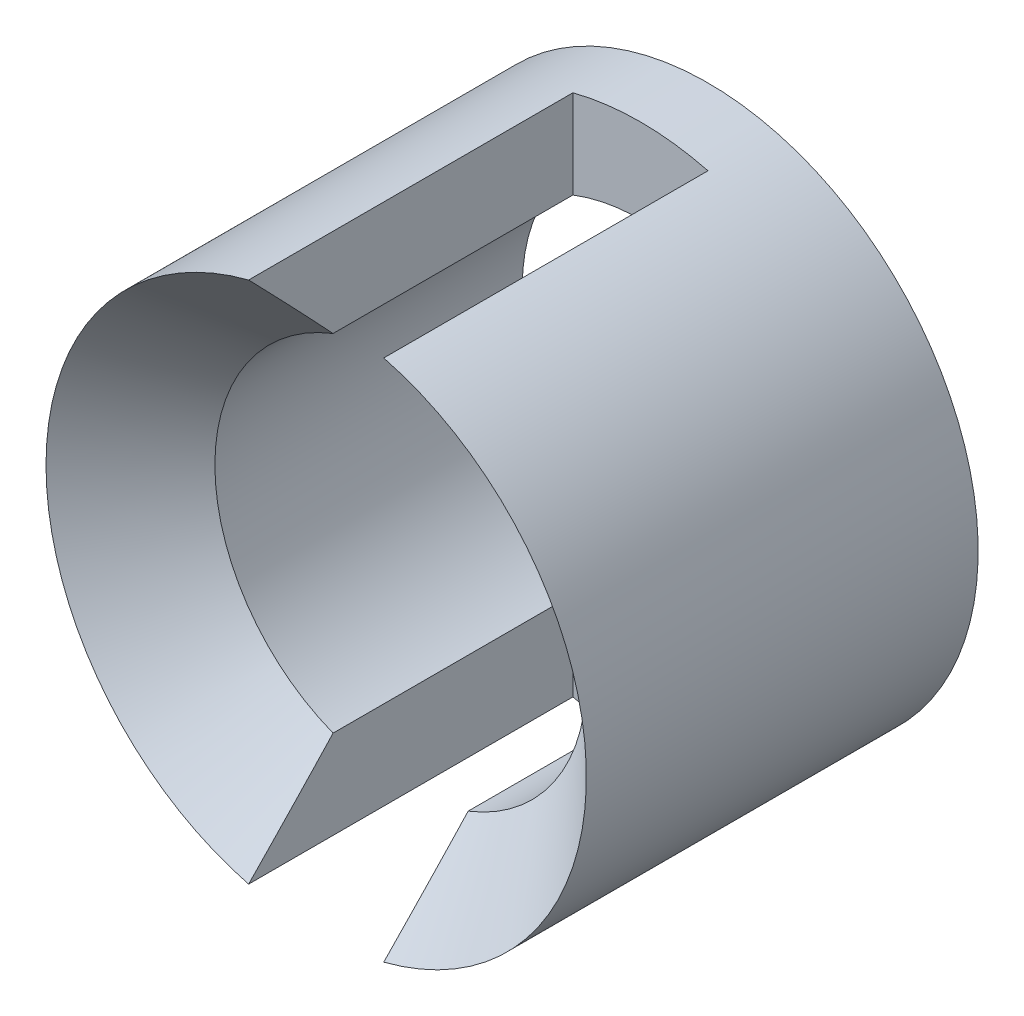
SolidWorks part; units mm, degrees
ref_plane "Ebene vorne" through (0, 0, 0) normal (0, 0, 1) x (1, 0, 0)
ref_plane "Ebene oben" through (0, 0, 0) normal (0, 1, 0) x (1, 0, 0)
ref_plane "Ebene rechts" through (0, 0, 0) normal (1, 0, 0) x (0, 0, -1)
sketch "Skizze2" plane through (0, 0, 0) normal (0, 1, 0) x (1, 0, 0)
  line L0 (48, -34) -> (52, -34) construction
  line L1 (52, -28) -> (52, -34) construction
  line L2 (52, -27) -> (52, -28) construction
  line L3 (52, -27) -> (48, -27) construction
  line L4 (48, -27) -> (48, -28) construction
  line L5 (48, -28) -> (48, -34) construction
  line L6 (48, -34) -> (52, -34)
  line L7 (52, -28) -> (52, -34)
  line L8 (52, -27) -> (52, -28)
  line L9 (52, -27) -> (48, -27)
  line L10 (48, -27) -> (48, -28)
  line L11 (48, -28) -> (48, -34)
revolve "Rotation1" add sketch "Skizze2" angle 360 about L7
hole_wizard "Formsenkung für M5 Linsensenkschraube mit Schlitz1" positions "Skizze4" profile "Skizze6" countersink size "M5" standard "DIN" end condition up to next
sketch "Skizze4" plane through (0, 0, 34) normal (0, 0, 1) x (1, 0, 0)
  point P0 (52, 0)
sketch "Skizze6" plane through (52, 0, 34) normal (1, 0, 0) x (0, -1, 0)
  line L0 (0, 0) -> (0, 7)
  line L1 (0, 7) -> (2.75, 7)
  line L2 (2.75, 7) -> (2.75, 2.45)
  line L3 (2.75, 2.45) -> (5.2, 0)
  line L5 (5.2, 0) -> (0, 0)
  line L6 (-2.75, 2.45) -> (-5.2, 0) construction
  line L11 (0, -6.35) -> (0, 107.95) construction
  dimension "Bohrerdurchmesser" = 5.5
  dimension "Bohrungstiefe" = 7
  dimension "Senkdurchmesser (Oben)" = 10.4
  dimension "Senkwinkel (Oben)" = 90
sketch "Skizze7" plane through (0, 0, 0) normal (0, 1, 0) x (1, 0, 0)
  line L0 (48, -34) -> (52, -34) construction
  line L1 (52, -28) -> (52, -34) construction
  line L2 (51, -28) -> (51, -34) construction
  line L3 (52, -28) -> (48, -28) construction
  line L4 (51, -34) -> (52, -34)
  line L5 (52, -28) -> (52, -34)
  line L6 (51, -28) -> (51, -34)
  line L7 (52, -28) -> (51, -28)
extrude "Schnitt-Linear austragen1" cut sketch "Skizze7" against normal through all both and the other way through all
mirror "Spiegeln1" about plane through (52, -4, 28) normal (1, 0, 0) of "Schnitt-Linear austragen1"
